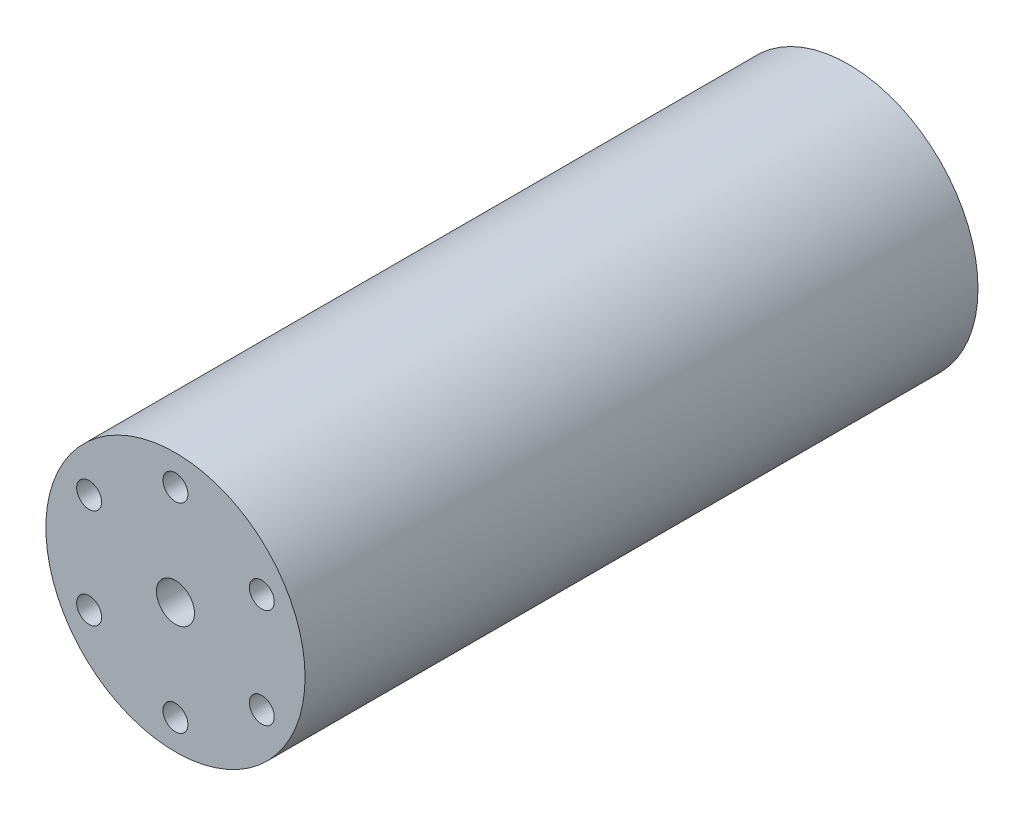
SolidWorks part; units mm, degrees
ref_plane "Front Plane" through (0, 0, 0) normal (0, 0, 1) x (1, 0, 0)
ref_plane "Top Plane" through (0, 0, 0) normal (0, 1, 0) x (1, 0, 0)
ref_plane "Right Plane" through (0, 0, 0) normal (1, 0, 0) x (0, 0, -1)
sketch "Sketch2" plane through (0, 0, 0) normal (0, 0, 1) x (1, 0, 0)
  circle A0 centre (0, 0) radius 26
  dimension "D1" = 52
extrude "Boss-Extrude1" add sketch "Sketch2" along normal blind 135 contours A0
sketch "Sketch3" plane through (0, 0, 0) normal (0, 0, -1) x (-1, 0, 0)
  circle A0 centre (0, 0) radius 3.815
  dimension "D1" = 7.63
extrude "Cut-Extrude1" cut sketch "Sketch3" against normal blind 135
sketch "Sketch5" plane through (0, 0, 0) normal (0, 0, -1) x (-1, 0, 0)
  circle A0 centre (0, 0) radius 18.5
  dimension "D1" = 37
extrude "Cut-Extrude2" cut sketch "Sketch5" against normal blind 30
sketch "Sketch6" plane through (0, 0, 135) normal (0, 0, 1) x (1, 0, 0)
  circle A0 centre (0, 20) radius 2.5
  circle A1 centre (17.3205, 10) radius 2.5
  circle A2 centre (17.3205, -10) radius 2.5
  circle A3 centre (0, -20) radius 2.5
  circle A4 centre (-17.3205, -10) radius 2.5
  circle A5 centre (-17.3205, 10) radius 2.5
  point P15 (0, 0)
  dimension "D1" = 20
  dimension "D2" = 5
  dimension "D3" = 6
extrude "Cut-Extrude3" cut sketch "Sketch6" against normal blind 5 contours A0
extrude "Cut-Extrude4" cut sketch "Sketch6<3>" against normal blind 5
sketch "Sketch6<3>" plane through (0, 0, 135) normal (0, 0, 1) x (1, 0, 0) same geometry as "Sketch6"
